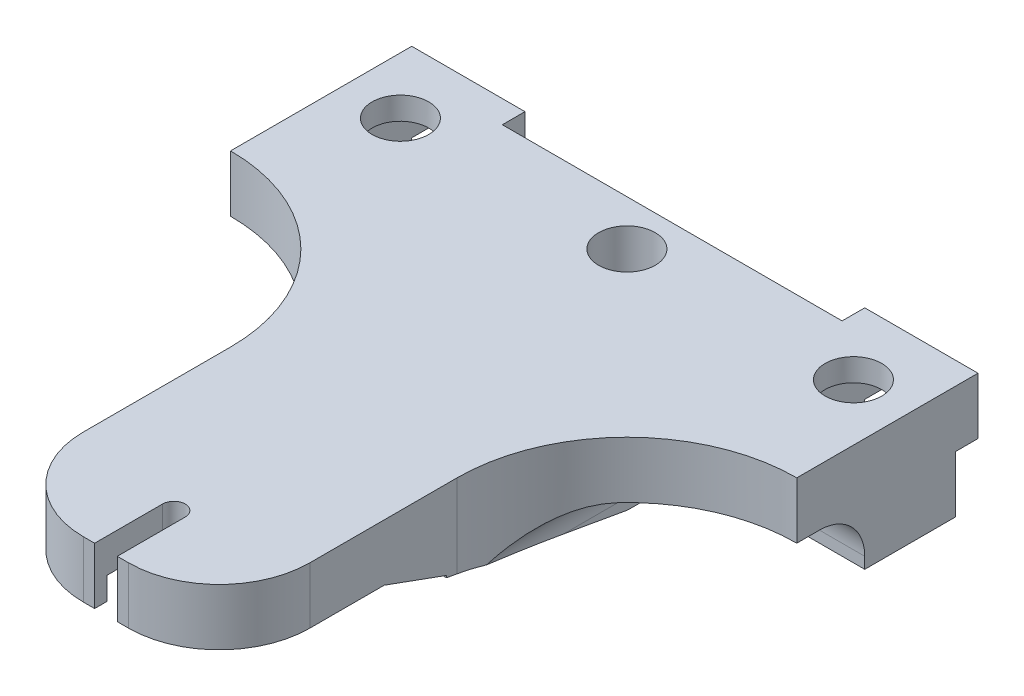
SolidWorks part; units mm, degrees
ref_plane "Front Plane" through (0, 0, 0) normal (0, 0, 1) x (1, 0, 0)
ref_plane "Top Plane" through (0, 0, 0) normal (0, 1, 0) x (1, 0, 0)
ref_plane "Right Plane" through (0, 0, 0) normal (1, 0, 0) x (0, 0, -1)
sketch "Sketch1" plane through (0, 0, 0) normal (0, 1, 0) x (1, 0, 0)
  line L0 (-0.5016, 44) -> (-15, 44)
  line L1 (-15, 44) -> (-15, 46)
  line L2 (-15, 46) -> (-25, 46)
  line L3 (-25, 46) -> (-25, 30)
  line L4 (-0.5016, 44) -> (15, 44)
  line L5 (15, 44) -> (15, 46)
  line L6 (15, 46) -> (25, 46)
  line L7 (25, 46) -> (25, 30)
  line L8 (-10, -6) -> (-10, 30)
  line L9 (-10, -6) -> (10, -6)
  line L10 (10, -6) -> (10, 30)
  line L11 (10, 30) -> (25, 30)
  line L12 (-10, 30) -> (-25, 30)
  line L14 (-1, 0) -> (1, 0)
  line L15 (-1, 0) -> (-1, -14.326)
  line L16 (-1, -14.326) -> (1, -14.326)
  line L17 (1, 0) -> (1, -14.326)
  circle A0 centre (0, 0) radius 1
  circle A1 centre (-20, 40) radius 2.5
  circle A2 centre (20, 40) radius 2.5
  circle A3 centre (0, 40) radius 2.5
  dimension "D1" = 40
  dimension "D3" = 20
  dimension "D4" = 2
  dimension "D5" = 5
  dimension "D6" = 5
  dimension "D7" = 5
  dimension "D2" = 20
  dimension "D8" = 40
  dimension "D9" = 25
  dimension "D10" = 25
  dimension "D11" = 15
  dimension "D12" = 15
  dimension "D13" = 2
  dimension "D14" = 2
  dimension "D15" = 44
  dimension "D16" = 30
  dimension "D17" = 30
  dimension "D18" = 6
  dimension "D19" = 10
  dimension "D20" = 10
  dimension "D21" = 40
extrude "Boss-Extrude1" add sketch "Sketch1" along normal blind 5 contours A0 L17 L9 L10 L11 L7 L6 L5 L4 L0 L1 L2 L3 L12 L8 L15 A3 A2 A1 region at (0, 0, -24.5179)
sketch "Sketch2" plane through (0, 0, 0) normal (0, 1, 0) x (1, 0, 0)
  circle A0 centre (0, 0) radius 5
  dimension "D1" = 10
extrude "Cut-Extrude1" cut sketch "Sketch2" along normal blind 2
fillet "Fillet1" radius 15 2 edges at (-10, 2.5, -30) (10, 2.5, -30)
fillet "Fillet2" radius 8 2 edges at (-10, 2.5, 6) (10, 2.5, 6)
sketch "Sketch3" plane through (0, 0, 0) normal (0, 1, 0) x (1, 0, 0)
  line L1 (-25, 44) -> (25, 44)
  line L2 (-25, 44) -> (-25, 36)
  line L3 (-25, 36) -> (25, 36)
  line L4 (25, 44) -> (25, 36)
  line L8 (-10, 14.067) -> (10, 14.067)
  line L9 (-10, 14.067) -> (-10, 36.3301)
  line L10 (-10, 36.3301) -> (10, 36.3301)
  line L11 (10, 14.067) -> (10, 36.3301)
  circle A1 centre (20, 40) radius 2.5
  circle A3 centre (0, 40) radius 2.5
  circle A5 centre (-20, 40) radius 2.5
  circle A7 centre (20, 40) radius 2.5 construction
  circle A8 centre (-20, 40) radius 2.5 construction
  circle A9 centre (0, 40) radius 2.5 construction
  dimension "D2" = 8
extrude "Boss-Extrude3" add sketch "Sketch3" against normal blind 5 contours L8 L11 L3 L9 | L11 L3 L4 L1 L2 L9 L10 | L3 L11 L10 L9 region at (0, 0, -43.4936) region at (0, 0, -36.1651) region at (0, 0, -25.0335)
chamfer "Chamfer1" distance 2 angle 70 1 edges at (0, 0, -14.067) first distance on face at (0, -2.5, -14.067)
chamfer "Chamfer2" distance 16 angle 10 1 edges at (0, -5, -14.067) first distance on face at (0, -5, -32.5167)
fillet "Fillet3" radius 4 4 edges at (-10, 0, -25.5) (-17.5, 0, -36) (10, 0, -25.5) (17.5, 0, -36)
sketch "Sketch4" plane through (0, 0, 0) normal (0, 0, 1) x (1, 0, 0)
  line L0 (25, -5) -> (25, 0) construction
  line L1 (23, 3) -> (17, 3)
  line L2 (23, 3) -> (23, -3)
  line L3 (23, -3) -> (17, -3)
  line L4 (17, 3) -> (17, -3)
  line L5 (-23, 3) -> (-17, 3)
  line L6 (-23, 3) -> (-23, -3)
  line L7 (-23, -3) -> (-17, -3)
  line L8 (-17, 3) -> (-17, -3)
  line L9 (-25, -5) -> (-25, 0) construction
  line L10 (-25, -5) -> (25, -5) construction
  dimension "D1" = 2
  dimension "D2" = 2
  dimension "D3" = 2
  dimension "D4" = 2
  dimension "D5" = 2
  dimension "D6" = 2
  dimension "D7" = 8
  dimension "D8" = 8
extrude "Cut-Extrude2" cut sketch "Sketch4" along normal blind 8 from offset 46 offset against normal yes
sketch "Sketch5" plane through (0, -5, 0) normal (0, -1, 0) x (1, 0, 0)
  circle A0 centre (0, -40) radius 2.5
  circle A1 centre (0, -40) radius 2.7154
  circle A2 centre (0, -40) radius 2.5 construction
extrude "Boss-Extrude4" add sketch "Sketch5" along normal blind 1
fillet "Fillet4" radius 5 1 edges at (0, -5, -37.2846)
sketch "Sketch6" plane through (0, 0, 0) normal (1, 0, 0) x (0, 0, -1)
  line L0 (-6, 0) -> (2, 0) construction
  circle A0 centre (0, 1.2) radius 0.5
  dimension "D2" = 1
  dimension "D1" = 1.2
extrude "Cut-Extrude3" cut sketch "Sketch6" against normal blind 10
